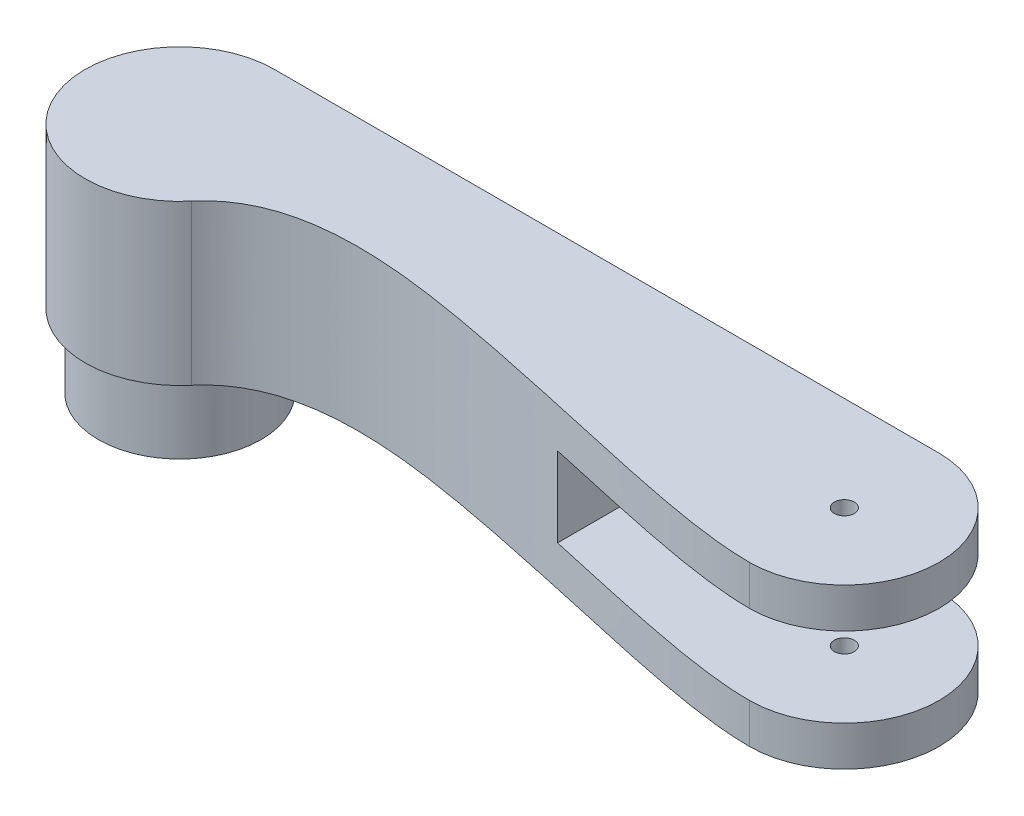
SolidWorks part; units mm, degrees
ref_plane "Front Plane" through (0, 0, 0) normal (0, 0, 1) x (1, 0, 0)
ref_plane "Top Plane" through (0, 0, 0) normal (0, 1, 0) x (1, 0, 0)
ref_plane "Right Plane" through (0, 0, 0) normal (1, 0, 0) x (0, 0, -1)
sketch "Sketch1" plane through (0, 0, 0) normal (0, 1, 0) x (1, 0, 0)
  line L0 (-50, 0) -> (50, 0) construction
  line L1 (-50, 14.25) -> (50, 14.25)
  line L2 (-50, -14.25) -> (50, -14.25)
  arc A0 (-50, 14.25) -> (-50, -14.25) centre (-50, 0) ccw
  arc A1 (50, -14.25) -> (50, 14.25) centre (50, 0) ccw
  point P3 (0, 0)
  dimension "D1" = 14.25
  dimension "D2" = 100
extrude "Boss-Extrude1" add sketch "Sketch1" along normal blind 6
sketch "Sketch3" plane through (0, 0, 0) normal (0, -1, 0) x (1, 0, 0)
  circle A0 centre (50, 0) radius 1.5
  dimension "D1" = 3
extrude "Cut-Extrude2" cut sketch "Sketch3" against normal through all
sketch "Sketch4" plane through (0, 6, 0) normal (0, 1, 0) x (1, 0, 0)
  line L0 (-50, 14.25) -> (15, 14.25)
  line L1 (-50, 14.25) -> (50, 14.25) construction
  line L2 (15, 14.25) -> (15, -14.25)
  line L3 (-50, -14.25) -> (50, -14.25) construction
  line L4 (15, -14.25) -> (-50, -14.25)
  arc A0 (-50, 14.25) -> (-50, -14.25) centre (-50, 0) ccw
  arc A1 (-50, 14.25) -> (-50, -14.25) centre (-50, 0) ccw construction
  dimension "D1" = 65
extrude "Boss-Extrude2" add sketch "Sketch4" along normal blind 12
sketch "Sketch5" plane through (0, 18, 0) normal (0, 1, 0) x (1, 0, 0)
  line L0 (-50, 0) -> (50, 0) construction
  line L1 (-50, 14.25) -> (50, 14.25)
  line L2 (-50, -14.25) -> (50, -14.25)
  arc A0 (-50, 14.25) -> (-50, -14.25) centre (-50, 0) ccw
  arc A1 (50, -14.25) -> (50, 14.25) centre (50, 0) ccw
  point P4 (0, 0)
  dimension "D1" = 14.25
extrude "Boss-Extrude3" add sketch "Sketch5" along normal blind 6
sketch "Sketch6" plane through (0, 24, 0) normal (0, 1, 0) x (1, 0, 0)
  circle A0 centre (50, 0) radius 1.5
  dimension "D1" = 3
extrude "Cut-Extrude3" cut sketch "Sketch6" against normal up to next
sketch "Sketch7" plane through (0, 24, 0) normal (0, 1, 0) x (1, 0, 0)
  line L0 (0, -13.2) -> (0, 13.2) construction
  line L1 (-50, -14.25) -> (50, -14.25)
  circle A0 centre (-50, 0) radius 14.25
  circle A1 centre (50, 0) radius 14.25
  spline S0 degree 3 poles (-39.0732, -9.1469) (-31.5141, -0.117) (5.4387, -4.6452) (38.6975, -14.25) (50, -14.25) knots 0 0 0 0 0.435908 1 1 1 1
  line M5 (-50, -14.25) -> (50, -14.25)
extrude "Cut-Extrude4" cut sketch "Sketch7" against normal up to next contours S0 A0 M5 region at (-8.5907, 24, 9.7914)
sketch "Sketch8" plane through (0, 0, 0) normal (0, -1, 0) x (1, 0, 0)
  circle A1 centre (-50, 0) radius 12.25
  dimension "D1" = 24.5
extrude "Boss-Extrude4" add sketch "Sketch8" along normal blind 11
sketch "Sketch9" plane through (0, -11, 0) normal (0, -1, 0) x (1, 0, 0)
  circle A0 centre (-50, 0) radius 8.25 construction
  circle A1 centre (-50, 8.25) radius 2.5
  circle A2 centre (-50, -8.25) radius 2.5
  arc A3 (-50, 14.25) -> (-50, -14.25) centre (-50, 0) ccw construction
  circle A4 centre (-50, 0) radius 3
  point P6 (-50, 0)
  dimension "D1" = 16.5
  dimension "D2" = 5
  dimension "D3" = 6
extrude "Cut-Extrude5" cut sketch "Sketch9" against normal blind 6
equation "\"Length\"= 100mm"
equation "\"Radius\"= 14.25mm"
equation "\"Thick\"= 12mm"
equation "\"D1@Sketch1\"= \"Radius\""
equation "\"D2@Sketch1\" = \"Length\""
equation "\"D1@Boss-Extrude1\"= \"Thick\""
equation "\"D1@Sketch4\"=\"Length\"*0.65"
equation "\"D1@Sketch5\"=\"Radius\""
equation "\"D1@Boss-Extrude2\"=\"Thick\""
equation "\"D1@Boss-Extrude4\"=\"Thick\"-1"
